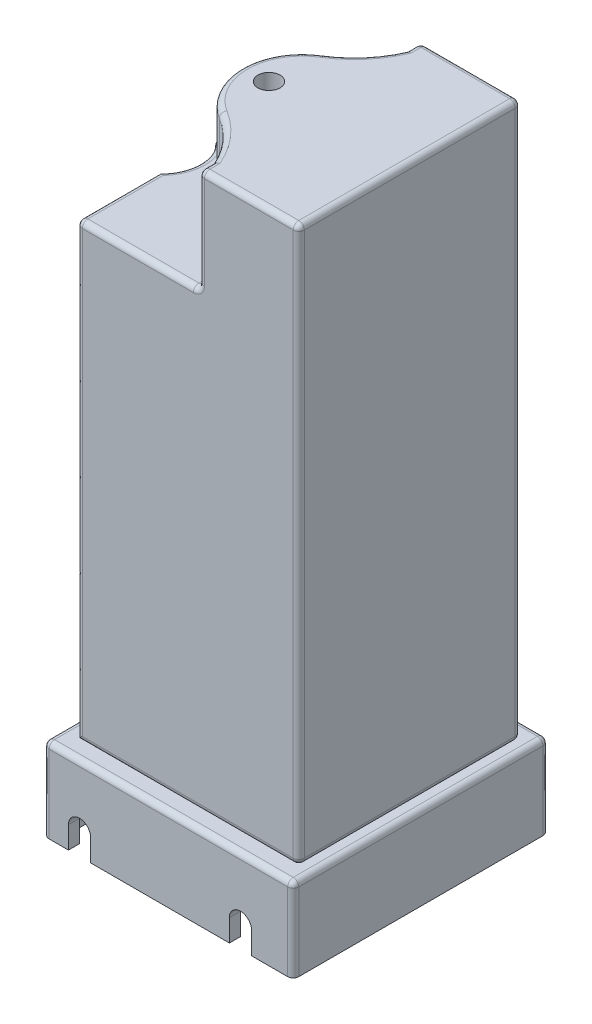
SolidWorks part; units mm, degrees
ref_plane "Front Plane" through (0, 0, 0) normal (0, 0, 1) x (1, 0, 0)
ref_plane "Top Plane" through (0, 0, 0) normal (0, 1, 0) x (1, 0, 0)
ref_plane "Right Plane" through (0, 0, 0) normal (1, 0, 0) x (0, 0, -1)
sketch "Sketch1" plane through (0, 0, 0) normal (0, 1, 0) x (1, 0, 0)
  line L1 (-200, -200) -> (200, -200)
  line L2 (-200, -200) -> (-200, 200)
  line L3 (-200, 200) -> (200, 200)
  line L4 (200, -200) -> (200, 200)
  line L5 (-200, -200) -> (200, 200) construction
  line L6 (-200, 200) -> (200, -200) construction
  point P0 (0, 0)
  dimension "D1" = 400
  dimension "D2" = 400
extrude "Boss-Extrude1" add sketch "Sketch1" along normal blind 1000
sketch "Sketch2" plane through (0, 0, 200) normal (0, 0, 1) x (1, 0, 0)
  line L0 (-200, 900) -> (20, 900)
  line L1 (-200, 1000) -> (-200, 0) construction
  line L2 (20, 900) -> (20, 812.4135)
  line L3 (20, 812.4135) -> (-200, 812.4135)
  line L4 (-200, 900) -> (-200, 812.4135)
  line L5 (-200, 1000) -> (200, 1000) construction
  line L6 (200, 1000) -> (200, 0) construction
  dimension "D1" = 100
  dimension "D2" = 180
extrude "Cut-Extrude1" cut sketch "Sketch2" against normal blind 1000
sketch "Sketch3" plane through (0, 1000, 0) normal (0, 1, 0) x (1, 0, 0)
  line L0 (20, 200) -> (20, -200) construction
  line L5 (-220, 0) -> (220, 0) construction
  line L7 (20, 200) -> (-200, 200)
  line L8 (-200, 200) -> (-200, -200)
  line L9 (-200, -200) -> (20, -200)
  line L11 (20, 174.0779) -> (20, 200)
  line L12 (20, -174.0779) -> (20, -200)
  arc A2 (-51.1058, 92.0718) -> (-51.1058, -92.0718) centre (5.9968, 0) ccw
  arc A4 (20, 174.0779) -> (-51.1058, 92.0718) centre (-147.4819, 247.4676) cw
  arc A5 (20, -174.0779) -> (-51.1058, -92.0718) centre (-147.4819, -247.4676) ccw
  line M4 (200, 200) -> (-200, 200)
  line M5 (-200, 200) -> (-200, -200)
  line M6 (-200, -200) -> (200, -200)
extrude "Cut-Extrude2" cut sketch "Sketch3" against normal up to next contours M4 M5 M6 region at (-113.6639, 1000, 0)
fillet "Fillet7" radius 10 3 edges at (-9.3279, 900, 127.6773) (-9.3279, 900, -127.6773) (-102.3448, 900, 0)
sketch "Sketch6" plane through (0, 812.4135, 0) normal (0, 1, 0) x (1, 0, 0)
  line L0 (-200, 200) -> (-200, -200)
  line L1 (-200, 50.4336) -> (-200, -50.4336)
  arc A0 (-200, 50.4336) -> (-200, -50.4336) centre (-248.9525, 0) cw
  point P8 (-200, 0)
extrude "Cut-Extrude3" cut sketch "Sketch6" against normal blind 1119 contours A0 L0 region at (-191.3455, 812.4135, 0)
sketch "Sketch7" plane through (-200, 0, 0) normal (-1, 0, 0) x (0, 0, 1)
  line L10 (199.0843, 709.2094) -> (-198.3802, 709.2094)
  line L11 (199.0843, 709.2094) -> (199.0843, 712.8999)
  line L12 (199.0843, 712.8999) -> (-198.3802, 712.8999)
  line L13 (-198.3802, 709.2094) -> (-198.3802, 712.8999)
extrude "Cut-Extrude4" cut sketch "Sketch7" against normal blind 51
pattern_linear "LPattern1" count 5 spacing 150 along (0, -1, 0) of "Cut-Extrude4"
sketch "Sketch8" plane through (0, 1000, 0) normal (0, 1, 0) x (1, 0, 0)
  circle A0 centre (-53.7308, 0) radius 20
  dimension "D1" = 40
extrude "Cut-Extrude5" cut sketch "Sketch8" against normal up to surface (100 mm away) up to face at (-22.4137, 900, 0)
fillet "Fillet8" radius 10 16 edges at (20, 906.2068, -200) (-90, 812.4135, 200) (-9.3279, 1000, -127.6773) (-9.3279, 1000, 127.6773) (20, 1000, -187.039) (20, 1000, 187.039) (110, 1000, -200) (200, 1000, 0) (110, 1000, 200) (-102.3448, 1000, 0) (-90, 812.4135, -200) (-178.6681, 812.4135, 0) (-200, 812.4135, 125.2168) (-200, 812.4135, -125.2168) (20, 812.4135, 0) (20, 906.2068, 200)
ref_plane "Plane1" through (0, 759.2094, 0) normal (0, 1, 0) x (1, 0, 0)
sketch "Sketch9" plane through (0, 759.2094, 0) normal (0, 1, 0) x (1, 0, 0)
  arc A2 (-192.8752, -42.3703) -> (-191.9733, 41.1493) centre (-161.5745, -0.9436) cw
ref_plane "Plane2" through (-192.8752, 759.2094, 42.3703) normal (-0.7979, 0, -0.6028) x (-0.6028, 0, 0.7979)
sketch "Sketch10" plane through (-192.8752, 759.2094, 42.3703) normal (-0.7979, 0, -0.6028) x (-0.6028, 0, 0.7979)
  circle A0 centre (0, 0) radius 7.5
  dimension "D1" = 15
sweep "Sweep1" add profiles "Sketch10" path "Sketch9"
pattern_linear "LPattern2" count 6 spacing 140 along (0, -1, 0) of "Sweep1"
fillet "Fillet9" radius 2 2 edges at (-189.1315, 764.698, -36.8964) (-196.7751, 763.5492, 47.0894)
fillet "Fillet10" radius 2 10 edges at (-189.1315, 64.698, -36.8964) (-196.7751, 63.5492, 47.0894) (-189.7501, 205.5842, -37.881) (-196.2673, 204.4587, 46.5207) (-189.7501, 345.5842, -37.881) (-196.2673, 344.4587, 46.5207) (-189.7501, 485.5842, -37.881) (-196.2673, 484.4587, 46.5207) (-189.1315, 624.698, -36.8964) (-196.7751, 623.5492, 47.0894)
fillet "Fillet11" radius 10 10 edges at (197.0711, 997.0711, 197.0711) (-197.0711, 809.4846, 197.0711) (-197.0711, 809.4846, -197.0711) (197.0711, 997.0711, -197.0711) (200, 495, 200) (0, 0, 200) (-200, 401.2068, 200) (-200, 401.2068, -200) (0, 0, -200) (200, 495, -200)
fillet "Fillet12" radius 10 3 edges at (197.0711, 2.9289, 197.0711) (197.0711, 2.9289, -197.0711) (200, 0, 0)
sketch "Sketch11" plane through (0, 0, 0) normal (0, -1, 0) x (-1, 0, 0)
  line L0 (200, -50.4336) -> (200, -190) construction
  line L1 (230, -230) -> (-220, -230)
  line L2 (230, -230) -> (230, 230)
  line L3 (230, 230) -> (-220, 230)
  line L4 (-220, -230) -> (-220, 230)
  line L5 (190, -200) -> (-190, -200) construction
  line L6 (-190, 190) -> (-190, -190) construction
  line L7 (-190, 200) -> (190, 200) construction
  dimension "D1" = 30
  dimension "D2" = 30
  dimension "D3" = 30
  dimension "D4" = 30
extrude "Boss-Extrude2" add sketch "Sketch11" along normal blind 150
sketch "Sketch12" plane through (0, -150, 0) normal (0, -1, 0) x (-1, 0, 0)
  line L0 (230, -230) -> (230, 230) construction
  line L1 (210, 210) -> (-200, 210)
  line L2 (210, 210) -> (210, -210)
  line L3 (210, -210) -> (-200, -210)
  line L4 (-200, 210) -> (-200, -210)
  line L5 (210, 210) -> (-200, -210) construction
  line L6 (210, -210) -> (-200, 210) construction
  line L7 (230, 230) -> (-220, 230) construction
  line L10 (-220, 230) -> (-220, -230) construction
  line L11 (-220, -230) -> (230, -230) construction
  point P0 (0, 0)
  dimension "D1" = 20
  dimension "D2" = 20
  dimension "D3" = 20
  dimension "D4" = 20
extrude "Cut-Extrude6" cut sketch "Sketch12" against normal blind 130
sketch "Sketch13" plane through (0, 0, 230) normal (0, 0, 1) x (1, 0, 0)
  line L0 (-165, -110.3285) -> (-165, -180.3285) construction
  line L1 (-145, -110.3285) -> (-145, -180.3285)
  line L2 (-185, -110.3285) -> (-185, -180.3285)
  line L3 (125, -110.3285) -> (125, -180.3285) construction
  line L4 (145, -110.3285) -> (145, -180.3285)
  line L5 (105, -110.3285) -> (105, -180.3285)
  line L6 (220, -150) -> (220, 0) construction
  arc A0 (-145, -110.3285) -> (-185, -110.3285) centre (-165, -110.3285) ccw
  arc A1 (-185, -180.3285) -> (-145, -180.3285) centre (-165, -180.3285) ccw
  arc A2 (145, -110.3285) -> (105, -110.3285) centre (125, -110.3285) ccw
  arc A3 (105, -180.3285) -> (145, -180.3285) centre (125, -180.3285) ccw
  point P2 (-165, -145.3285)
  point P7 (125, -145.3285)
  dimension "D1" = 20
  dimension "D2" = 20
  dimension "D3" = 70
  dimension "D4" = 70
  dimension "D5" = 250
  dimension "D6" = 75
extrude "Cut-Extrude7" cut sketch "Sketch13" against normal through all
fillet "Fillet13" radius 10 8 edges at (220, -75, 230) (220, 0, 0) (220, -75, -230) (-5, 0, -230) (-230, -75, -230) (-230, -75, 230) (-230, 0, 0) (-5, 0, 230)
